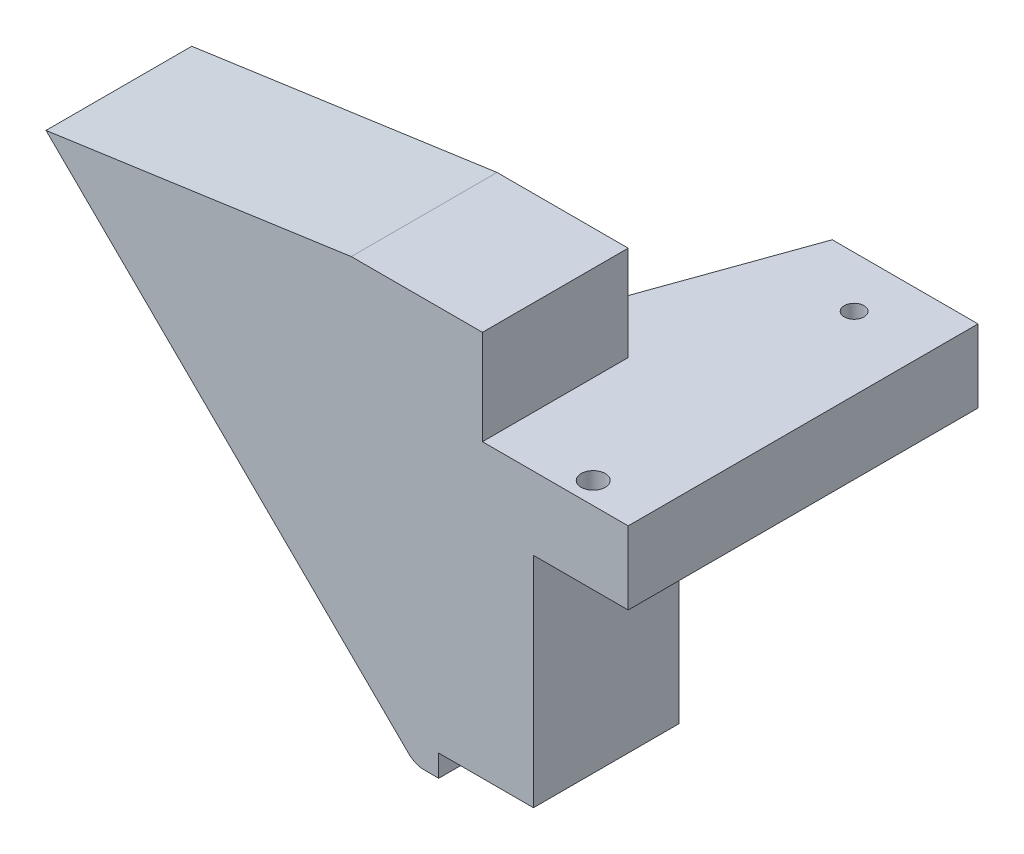
SolidWorks part; units mm, degrees
ref_plane "Front" through (0, 0, 0) normal (0, 0, 1) x (1, 0, 0)
ref_plane "Top" through (0, 0, 0) normal (0, 1, 0) x (1, 0, 0)
ref_plane "Right" through (0, 0, 0) normal (1, 0, 0) x (0, 0, -1)
sketch "草图1" plane through (0, 0, 0) normal (0, 0, 1) x (1, 0, 0)
  line L0 (0, 0) -> (0, 40)
  line L1 (0, 40) -> (-5, 40)
  line L2 (0, 0) -> (-5, 0)
  line L3 (-5, 0) -> (-5, -3)
  line L4 (-5, -3) -> (-13, -3)
  line L5 (-5, 53) -> (-23, 53)
  line L6 (-5, 40) -> (-5, 53)
  line L8 (-15.1213, -2.1213) -> (-64.8886, 47.0507)
  line L10 (-23, 53) -> (-64.8886, 47.0507)
  arc A0 (-15.1213, -2.1213) -> (-13, -3) centre (-13, 0) ccw
extrude "凸台-拉伸1" add sketch "草图1" along normal blind 172
shell "抽壳1" thickness 6
sketch "草图2" plane through (0, 0, 0) normal (1, 0, 0) x (0, 0, -1)
  line L1 (-154, 2) -> (-154, 18)
  line L2 (-154, 18) -> (-118, 18)
  line L3 (-118, 18) -> (-118, 2)
  line L4 (-54, 2) -> (-54, 18)
  line L5 (-54, 18) -> (-18, 18)
  line L6 (-18, 2) -> (-18, 18)
  line L7 (-54, 2) -> (-18, 2)
  line L9 (-154, 2) -> (-118, 2)
extrude "切除-拉伸1" cut sketch "草图2" against normal blind 74
ref_plane "基准面1" through (0, 0, 86) normal (0, 0, -1) x (-1, 0, 0)
sketch "草图3" plane through (0, 0, 86) normal (0, 0, -1) x (-1, 0, 0)
  line L0 (5, 53) -> (5, 40)
  line L1 (5, 40) -> (0, 40)
  line L2 (0, 40) -> (0, 0)
  line L3 (0, 0) -> (5, 0)
  line L4 (5, 0) -> (5, -3)
  line L5 (5, -3) -> (13, -3)
  line L6 (13, -3) -> (16.5794, -0.6807)
  line L7 (64.8886, 47.0507) -> (15.1213, -2.1213) construction
  line L8 (16.5794, -0.6807) -> (64.8886, 47.0507)
  line L9 (64.8886, 47.0507) -> (23, 53)
  line L10 (23, 53) -> (5, 53)
extrude "凸台-拉伸2" add sketch "草图3" along normal mid plane 4 contours L8 L9 L10 L0 L1 L2 L3 L4 L5 L6
sketch "草图4" plane through (0, 0, 172) normal (0, 0, 1) x (1, 0, 0)
  circle A0 centre (-15, 21.0713) radius 10
extrude "切除-拉伸2" cut sketch "草图4" against normal blind 186
sketch "草图5" plane through (0, 53, 0) normal (0, 1, 0) x (1, 0, 0)
  circle A1 centre (-13.3382, -63.5) radius 1.5
  circle A2 centre (-13.3382, -108.5) radius 1.5
extrude "切除-拉伸3" cut sketch "草图5" against normal blind 10
sketch "草图6" plane through (0, 0, 172) normal (0, 0, 1) x (1, 0, 0)
  line L0 (-11, 6) -> (-14.8042, 6)
  line L1 (-52.062, 42.8122) -> (-11.7678, 3) construction
  line L2 (-14.8042, 6) -> (-11.7678, 3)
  line L3 (-11.7678, 3) -> (-11, 3)
  line L4 (-11, 3) -> (-11, 6)
extrude "凸台-拉伸3" add sketch "草图6" against normal blind 172
sketch "草图7" plane through (0, 0, 0) normal (1, 0, 0) x (0, 0, -1)
  line L0 (-154, 18) -> (-154, 2)
  line L1 (-154, 2) -> (-118, 2)
  line L2 (-118, 2) -> (-118, 18)
  line L3 (-118, 18) -> (-154, 18)
  line L4 (-54, 18) -> (-54, 2)
  line L5 (-54, 2) -> (-18, 2)
  line L6 (-18, 2) -> (-18, 18)
  line L7 (-18, 2) -> (-18, 18) construction
  line L8 (-18, 18) -> (-54, 18) construction
  line L9 (-18, 18) -> (-54, 18)
extrude "切除-拉伸4" cut sketch "草图7" against normal blind 172
sketch "草图8" plane through (0, -3, 0) normal (0, -1, 0) x (1, 0, 0)
  line L0 (-5, 172) -> (-11, 172)
  line L1 (-13, 172) -> (-5, 172) construction
  line L2 (-11, 172) -> (-11, 0)
  line L3 (-13, 0) -> (-5, 0) construction
  line L4 (-11, 0) -> (-5, 0)
  line L5 (-5, 0) -> (-5, 172)
extrude "切除-拉伸5" cut sketch "草图8" against normal blind 3
sketch "草图9" plane through (0, 0, 0) normal (1, 0, 0) x (0, 0, -1)
  line L0 (-86, 40) -> (-151, 40)
  line L1 (-172, 40) -> (0, 40) construction
  line L2 (-151, 40) -> (-151, 35)
  line L3 (-151, 35) -> (-86, 35)
  line L4 (-86, -55) -> (-86, 55) construction
  line L5 (-86, 35) -> (-21, 35)
  line L6 (-21, 35) -> (-21, 40)
  line L7 (-21, 40) -> (-86, 40)
extrude "凸台-拉伸4" add sketch "草图9" along normal blind 15
chamfer "倒角1" distance 15 angle 45 1 edges at (15, 37.5, 151)
chamfer "倒角2" distance 15 angle 45 1 edges at (15, 37.5, 21)
chamfer "倒角3" distance 8 angle 45 1 edges at (0, 35, 86)
sketch "草图10" plane through (0, 0, 0) normal (0, -1, 0) x (1, 0, 0)
  circle A2 centre (-5, 158) radius 1.35
  circle A3 centre (-5, 111) radius 1.35
  circle A4 centre (-5, 61) radius 1.35
  circle A5 centre (-5, 14.0136) radius 1.35
extrude "切除-拉伸6" cut sketch "草图10" against normal blind 15
sketch "草图12" plane through (0, 40, 0) normal (0, 1, 0) x (1, 0, 0)
  line L2 (55, -86) -> (-55, -86) construction
  circle A1 centre (5, -41) radius 1.35
  circle A2 centre (5, -86) radius 1.35
  circle A3 centre (5, -131) radius 1.35
extrude "切除-拉伸7" cut sketch "草图12" against normal blind 15
sketch "草图14" plane through (0, 0, 0) normal (1, 0, 0) x (0, 0, -1)
  line L0 (-83.1596, 53) -> (-83.1596, -3)
  line L1 (-172, 53) -> (0, 53) construction
  line L2 (-172, -3) -> (0, -3) construction
  line L3 (-83.1596, -3) -> (-68.1596, -3)
  line L4 (-68.1596, -3) -> (-68.1596, 53)
  line L5 (-68.1596, 53) -> (-83.1596, 53)
extrude "切除-拉伸8" cut sketch "草图14" against normal mid plane 165 flip side to cut
sketch "草图15" plane through (0, 0, 68.1596) normal (0, 0, -1) x (-1, 0, 0)
  line L0 (0, 0) -> (-2, 0)
  line L1 (-2, 0) -> (-2, 29)
  line L2 (-8, 35) -> (0, 27) construction
  line L3 (-2, 29) -> (0, 27)
  line L4 (0, 27) -> (0, 0)
extrude "凸台-拉伸5" add sketch "草图15" against normal blind 15
sketch "草图16" plane through (0, 0, 68.1596) normal (0, 0, -1) x (-1, 0, 0)
  line L0 (-2, 29) -> (-2, 35)
  line L1 (-8, 35) -> (-2, 35)
  line L2 (-8, 35) -> (-2, 29)
extrude "切除-拉伸9" cut sketch "草图16" against normal blind 15
sketch "草图17" plane through (0, 0, 68.1596) normal (0, 0, -1) x (-1, 0, 0)
  line L0 (-15, 35) -> (-15, 30)
  line L1 (-15, 30) -> (-2, 30)
  line L2 (-2, 35) -> (-2, 0) construction
  line L3 (-2, 30) -> (-2, 35)
  line L4 (-2, 35) -> (-15, 35)
extrude "凸台-拉伸6" add sketch "草图17" against normal blind 15
sketch "草图18" plane through (0, 0, 68.1596) normal (0, 0, -1) x (-1, 0, 0)
  line L0 (-15, 40) -> (-15, 30)
  line L1 (-15, 30) -> (-2, 30)
  line L2 (-2, 30) -> (-2, 0)
  line L3 (-2, 0) -> (11, 0)
  line L4 (11, 0) -> (11, -3)
  line L5 (11, -3) -> (13, -3)
  line L6 (15.1213, -2.1213) -> (64.8886, 47.0507)
  line L7 (64.8886, 47.0507) -> (23, 53)
  line L8 (23, 53) -> (5, 53)
  line L9 (5, 53) -> (5, 40)
  line L10 (5, 40) -> (-15, 40)
  arc A0 (13, -3) -> (15.1213, -2.1213) centre (13, 0) ccw
extrude "凸台-拉伸7" add sketch "草图18" against normal blind 20 contours L10 L0 L1 L2 L3 L4 L5 A0 L6 L7 L8 L9
shell "抽壳2" thickness 10 removed face at (-9.5081, 23.7265, 88.1596)
sketch "草图20" plane through (0, 0, 88.1596) normal (0, 0, 1) x (1, 0, 0)
  line L0 (15, 40) -> (-15, 40)
  line L1 (-15, 43) -> (-15, 30) construction
  line L2 (-15, 40) -> (-15, 30)
  line L3 (-15, 30) -> (-8, 30)
  line L4 (-8, 30) -> (-8, 10) construction
  line L5 (-8, 30) -> (-8, 10) construction
  line L6 (-8, 30) -> (-8, 22)
  line L7 (-8, 22) -> (2, 22)
  line L8 (2, 30) -> (2, 0) construction
  line L9 (2, 22) -> (2, 30)
  line L10 (2, 30) -> (15, 30)
  line L11 (15, 30) -> (15, 40)
extrude "凸台-拉伸8" add sketch "草图20" along normal blind 28
sketch "草图21" plane through (2, 0, 0) normal (1, 0, 0) x (0, 0, -1)
  line L0 (-116.1596, 30) -> (-88.1596, 22)
  line L1 (-88.1596, 22) -> (-116.1596, 22)
  line L2 (-116.1596, 22) -> (-116.1596, 30)
extrude "切除-拉伸10" cut sketch "草图21" against normal blind 20
sketch "草图22" plane through (0, 40, 0) normal (0, 1, 0) x (1, 0, 0)
  line L1 (-8, -116.1596) -> (-15, -116.1596)
  line L2 (-15, -116.1596) -> (-15, -88.1596)
  line L4 (15, -116.1596) -> (-15, -116.1596) construction
  line L5 (-5, -116.1596) -> (-8, -116.1596)
  line L6 (-5, -116.1596) -> (-15, -88.1596)
extrude "切除-拉伸11" cut sketch "草图22" against normal blind 20
sketch "草图23" plane through (0, 40, 0) normal (0, 1, 0) x (1, 0, 0)
  circle A0 centre (7.2, -71.1596) radius 1.65
  circle A1 centre (5, -109.1596) radius 1.35
extrude "切除-拉伸12" cut sketch "草图23" against normal blind 22
sketch "草图26" plane through (0, 0, 0) normal (0, -1, 0) x (1, 0, 0)
  circle A0 centre (-5, 78.1596) radius 1.35
extrude "切除-拉伸14" cut sketch "草图26" against normal blind 10
ref_plane "基准面2" through (0, 0, 126.1596) normal (0, 0, 1) x (1, 0, 0)
mirror "镜向2" about plane through (0, 0, 126.1596) normal (0, 0, 1) of bodies 122
sketch "草图27" plane through (0, 40, 0) normal (0, 1, 0) x (1, 0, 0)
  line L0 (-70.3044, -126.4277) -> (59.1643, -124.0691)
  line L1 (59.1643, -124.0691) -> (93.5456, -94.9693)
  line L2 (93.5456, -94.9693) -> (93.5456, -36.4889)
  line L3 (93.5456, -36.4889) -> (-105.0779, -19.2641)
  line L4 (-105.0779, -19.2641) -> (-117.9336, -88.8971)
  line L5 (-117.9336, -88.8971) -> (-70.3044, -126.4277)
extrude "切除-拉伸15" cut sketch "草图27" against normal mid plane 165
